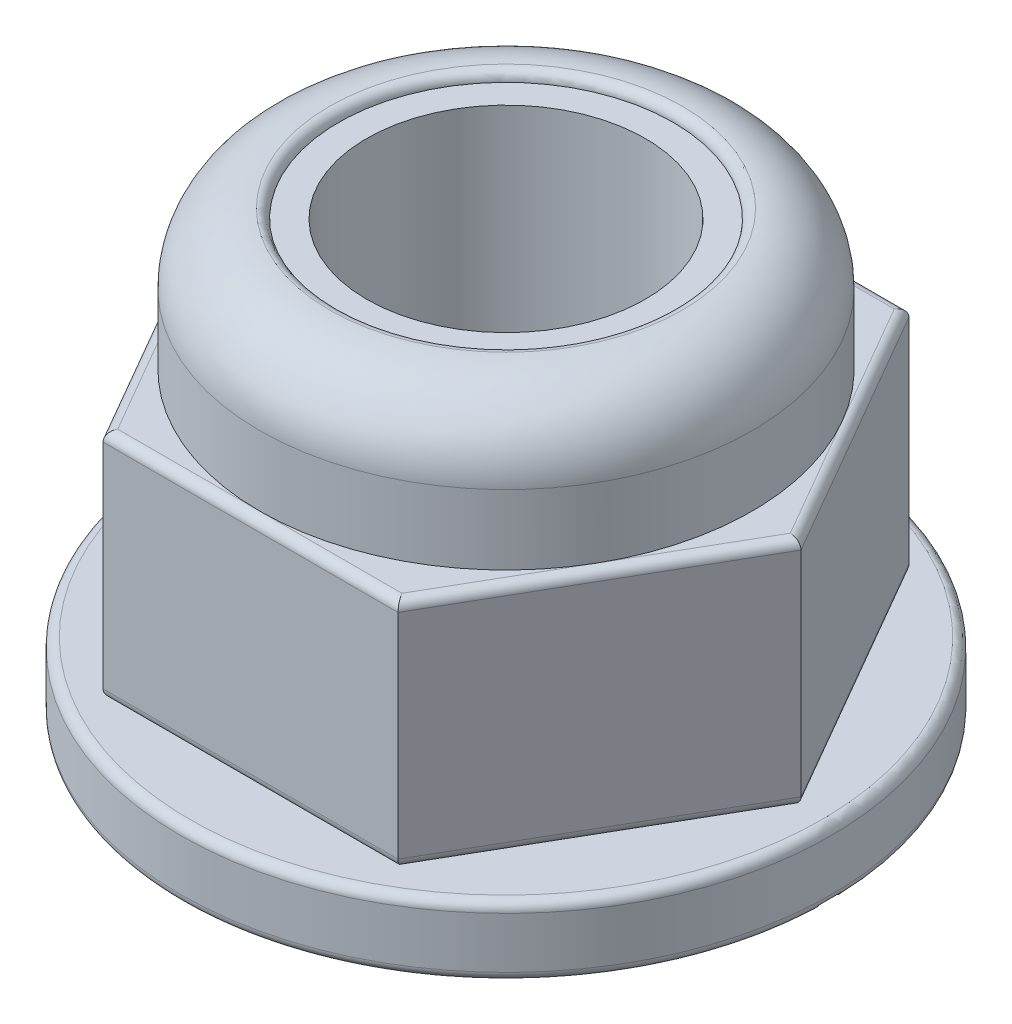
SolidWorks part; units mm, degrees
ref_plane "Front Plane" through (0, 0, 0) normal (0, 0, 1) x (1, 0, 0)
ref_plane "Top Plane" through (0, 0, 0) normal (0, 1, 0) x (1, 0, 0)
ref_plane "Right Plane" through (0, 0, 0) normal (1, 0, 0) x (0, 0, -1)
sketch "Sketch1" plane through (0, 0, 0) normal (0, 1, 0) x (1, 0, 0)
  line L1 (1.5877, -2.75) -> (3.1754, 0)
  line L2 (3.1754, 0) -> (1.5877, 2.75)
  line L3 (1.5877, 2.75) -> (-1.5877, 2.75)
  line L4 (-1.5877, 2.75) -> (-3.1754, 0)
  line L5 (-3.1754, 0) -> (-1.5877, -2.75)
  line L6 (-1.5877, -2.75) -> (1.5877, -2.75)
  circle A0 centre (0, 0) radius 2.75 construction
  circle A1 centre (0, 0) radius 1.5
  dimension "D1" = 3
  dimension "D2" = 5.5
extrude "Boss-Extrude1" add sketch "Sketch1" along normal blind 4
sketch "Sketch2" plane through (0, 0, 0) normal (1, 0, 0) x (0, 0, -1)
  line L0 (0, 4) -> (-2.75, 4) construction
  line L1 (-2.65, 3.25) -> (-2.65, 2.5)
  line L2 (-2.75, 4) -> (-2.75, 0) construction
  line L3 (-2.65, 2.5) -> (-5.25, 2.5)
  line L4 (-5.25, 2.5) -> (-5.25, 4)
  line L5 (-1.9, 4) -> (-1.9, 4.1)
  line L6 (0, 0) -> (-2.75, 0) construction
  line L7 (0, 4) -> (0, 0) construction
  line L8 (-1.9, 4.1) -> (-5.25, 4.1)
  line L9 (-5.25, 4.1) -> (-5.25, 4)
  arc A0 (-1.9, 4) -> (-2.65, 3.25) centre (-1.9, 3.25) ccw
  dimension "D1" = 0.75
  dimension "D2" = 0.1
  dimension "D3" = 2.5
  dimension "D4" = 0.1
  dimension "D5" = 2.5
revolve "Cut-Revolve3" cut sketch "Sketch2" angle 360 about L7
fillet "Fillet1" radius 0.1 13 edges at (0, 0, 1.5) (2.3816, 0, 1.375) (2.3816, 0, -1.375) (0, 0, -2.75) (-2.3816, 0, -1.375) (-2.3816, 0, 1.375) (0, 0, 2.75) (0, 2.5, -2.75) (2.3816, 2.5, 1.375) (0, 2.5, 2.75) (2.3816, 2.5, -1.375) (-2.3816, 2.5, -1.375) (-2.3816, 2.5, 1.375)
sketch "Sketch3" plane through (0, 4, 0) normal (0, 1, 0) x (1, 0, 0)
  circle A0 centre (0, 0) radius 1.8
  circle A1 centre (0, 0) radius 1.5
  circle A2 centre (0, 0) radius 1.5 construction
  dimension "D1" = 0.3
extrude "Cut-Extrude1" cut sketch "Sketch3" against normal blind 0.1
fillet "Fillet2" radius 0.1 1 edges at (0, 4, 1.8)
sketch "Sketch4" plane through (0, 0, 0) normal (0, -1, 0) x (1, 0, 0)
  circle A0 centre (0, 0) radius 1.5
  circle A1 centre (0, 0) radius 3.5
  circle A2 centre (0, 0) radius 1.5 construction
  dimension "D1" = 7
extrude "Boss-Extrude2" add sketch "Sketch4" along normal blind 0.75
fillet "Fillet3" radius 0.1 4 edges at (0, -0.75, -1.5) (0, -0.75, -3.5) (0, 0, -1.5) (0, 0, -3.5)
